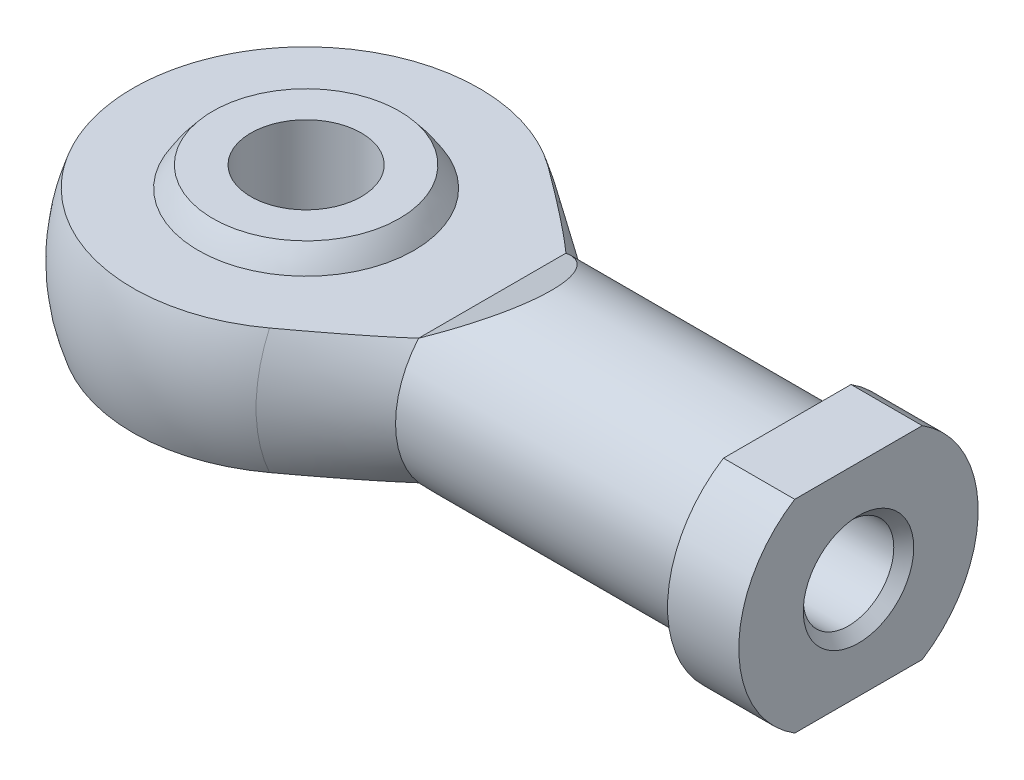
SolidWorks part; units mm, degrees
ref_plane "Ebene vorne" through (0, 0, 0) normal (0, 0, 1) x (1, 0, 0)
ref_plane "Ebene oben" through (0, 0, 0) normal (0, 1, 0) x (1, 0, 0)
ref_plane "Ebene rechts" through (0, 0, 0) normal (1, 0, 0) x (0, 0, -1)
sketch "Skizze1" plane through (0, 0, 0) normal (0, 0, 1) x (1, 0, 0)
  line L0 (5.5804, 8.2981) -> (10.11, 5.252)
  line L1 (10.11, 5.252) -> (26.13, 5.252)
  line L2 (26.13, 5.252) -> (26.13, 6.5)
  line L3 (26.13, 6.5) -> (30, 6.5)
  line L4 (30, 6.5) -> (30, 0)
  line L5 (30, 0) -> (-10, 0)
  line L6 (30, 0) -> (-10, 0) construction
  arc A0 (-10, 0) -> (5.5804, 8.2981) centre (0, 0) cw
revolve "Rotation1" add sketch "Skizze1" angle 360 about L6
sketch "Skizze2" plane through (0, 0, 0) normal (0, 0, 1) x (1, 0, 0)
  line L0 (-12, -10.1) -> (21.7147, -10.1)
  line L1 (21.7147, -10.1) -> (10.11, -3.4)
  line L2 (10.11, -3.4) -> (-11, -3.4)
  line L3 (-11, -3.4) -> (-11, 3.4)
  line L4 (-11, 3.4) -> (10.11, 3.4)
  line L5 (10.11, 3.4) -> (21.7147, 10.1)
  line L6 (21.7147, 10.1) -> (-12, 10.1)
  line L7 (-12, 10.1) -> (-12, -10.1)
extrude "Schnitt-Linear austragen1" cut sketch "Skizze2" along normal blind 10 and the other way blind 10
ref_plane "Ebene1" through (30, 0, 0) normal (1, 0, 0) x (0, 0, -1)
sketch "Skizze3" plane through (30, 0, 0) normal (1, 0, 0) x (0, 0, -1)
  line L0 (10.5, -10.5) -> (10.5, -5.5)
  line L1 (10.5, -5.5) -> (-8.5, -5.5)
  line L2 (-8.5, -5.5) -> (-8.5, 5.5)
  line L3 (-8.5, 5.5) -> (10.5, 5.5)
  line L4 (10.5, 5.5) -> (10.5, 10.5)
  line L5 (10.5, 10.5) -> (-10.5, 10.5)
  line L6 (-10.5, 10.5) -> (-10.5, -10.5)
  line L7 (-10.5, -10.5) -> (10.5, -10.5)
extrude "Schnitt-Linear austragen2" cut sketch "Skizze3" along normal blind 12 and the other way blind 12
hole_wizard "Bohrung1" positions "Skizze5" profile "Skizze4" legacy
sketch "Skizze5" plane through (30, 0, 0) normal (1, 0, 0) x (0, 0, -1)
  point P0 (0, 0)
sketch "Skizze4" plane through (30, 0, 0) normal (0, 1, 0) x (0, 0, -1)
  line L0 (0, 0) -> (0, 16.4194)
  line L1 (0, 16.4194) -> (2.4585, 15)
  line L2 (2.4585, 15) -> (2.4585, 0.5415)
  line L3 (2.4585, 0.5415) -> (3, 0)
  line L4 (3, 0) -> (0, 0)
  line L5 (0, -14.3089) -> (0, 102.4216) construction
  line L6 (0, 16.4194) -> (-2.4585, 15) construction
  line L7 (-2.4585, 0.5415) -> (-3, 0) construction
  dimension "Durchmesser" = 4.917
  dimension "Tiefe" = 15
  dimension "Senkdurchmesser1" = 6
  dimension "Senkwinkel1" = 90
  dimension "Spitzenwinkel" = 120
cosmetic thread "Gewindedarstellung1" parameters "D1"=12, "D2"=6
sketch "Skizze6" plane through (0, 0, 0) normal (0, 0, 1) x (1, 0, 0)
  line L0 (0, 3.4) -> (5.5922, 3.4)
  line L1 (5.5922, -3.4) -> (0, -3.4)
  line L2 (0, -3.4) -> (0, 3.4)
  line L3 (0, -3.4) -> (0, 3.4) construction
  arc A0 (5.5922, 3.4) -> (5.4362, 3.1302) centre (5.5922, 3.22) ccw
  arc A1 (5.4362, 3.1302) -> (5.4362, -3.1302) centre (0, 0) cw
  arc A2 (5.4362, -3.1302) -> (5.5922, -3.4) centre (5.5922, -3.22) ccw
revolve "Schnitt-Rotation1" cut sketch "Skizze6" angle 360 about L3
sketch "Skizze7" plane through (0, 0, 0) normal (0, 0, 1) x (1, 0, 0)
  line L0 (3, 4.5) -> (3, -4.5)
  line L1 (3, -4.5) -> (5.062, -4.5)
  line L2 (5.062, 4.5) -> (3, 4.5)
  line L3 (0, -4.5) -> (0, 4.5) construction
  arc A0 (5.062, -4.5) -> (5.062, 4.5) centre (0, 0) ccw
revolve "Rotation2" add sketch "Skizze7" angle 360 about L3
ref_plane "Ebene2" through (0, 0, 0) normal (0, 1, 0) x (1, 0, 0)
ref_plane "Ebene3" through (0, 0, 0) normal (0, 1, 0) x (1, 0, 0)
ref_plane "Ebene4" through (33.2, 0, 0) normal (1, 0, 0) x (0, 0, -1)
ref_plane "ANBAU XY" through (30, 0, 0) normal (1, 0, 0) x (0, 0, -1)
ref_plane "ANBAU XZ" through (0, 0, 0) normal (0, 0, -1) x (-1, 0, 0)
ref_plane "ANBAU YZ" through (0, 0, 0) normal (0, 1, 0) x (1, 0, 0)
ref_axis "ANBAU X" through (30, -50, 0) along (0, 1, 0)
ref_axis "ANBAU Y" through (30, 0, -80.9) along (0, 0, 1)
ref_axis "ANBAU Z" through (80.9, 0, 0) along (-1, 0, 0)
sketch3d "ANBAU"
  point P0 (30, 0, 0)
ref_plane "BOCK XY" through (0, 0, 0) normal (0, 1, 0) x (1, 0, 0)
ref_plane "BOCK XZ" through (0, 0, 0) normal (0, 0, 1) x (1, 0, 0)
ref_plane "BOCK YZ" through (0, 0, 0) normal (1, 0, 0) x (0, 0, -1)
ref_axis "BOCK X" through (-80.9, 0, 0) along (1, 0, 0)
ref_axis "BOCK Y" through (0, 0, 50) along (0, 0, -1)
ref_axis "BOCK Z" through (0, 50, 0) along (0, -1, 0)
sketch3d "BOCK"
  point P0 (0, 0, 0)
